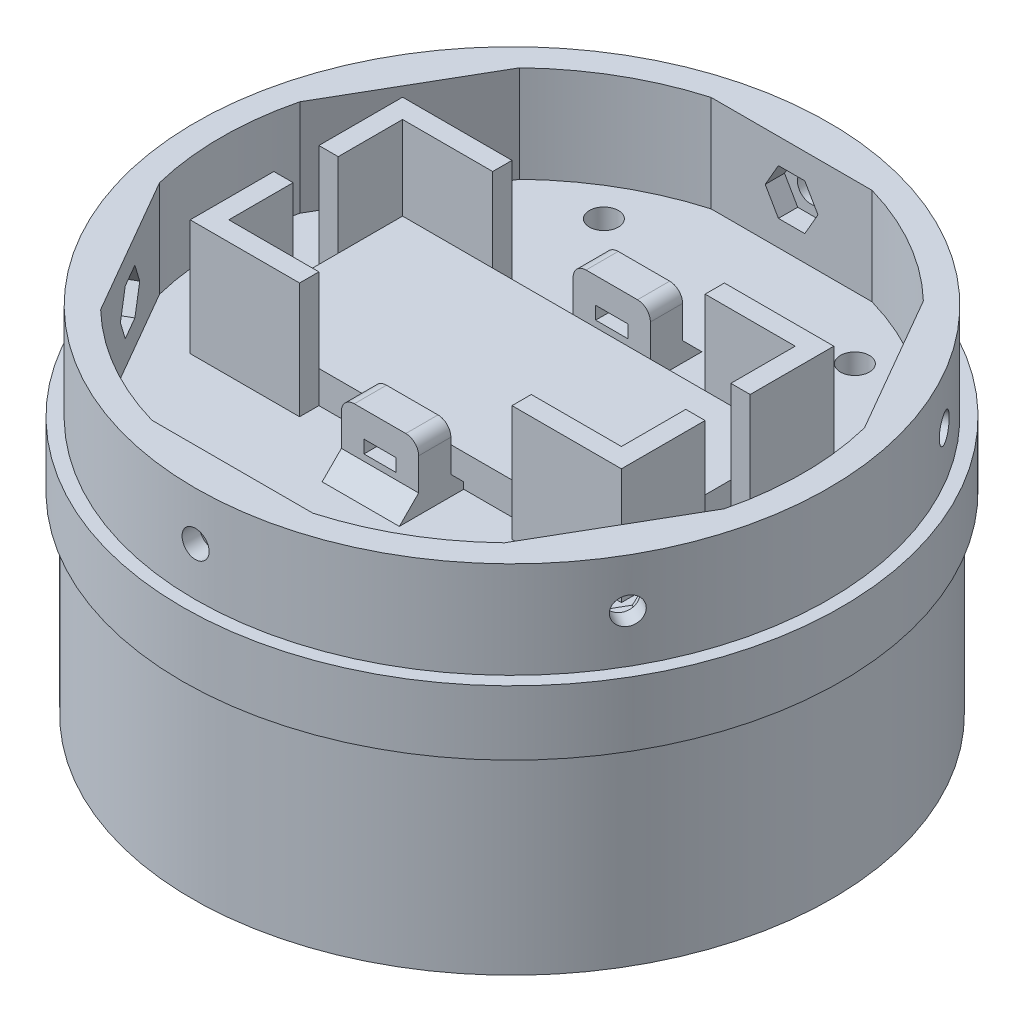
SolidWorks part; units mm, degrees
ref_plane "Спереди" through (0, 0, 0) normal (0, 0, 1) x (1, 0, 0)
ref_plane "Сверху" through (0, 0, 0) normal (0, 1, 0) x (1, 0, 0)
ref_plane "Справа" through (0, 0, 0) normal (1, 0, 0) x (0, 0, -1)
sketch "Эскиз1" plane through (0, 0, 0) normal (0, 0, 1) x (1, 0, 0)
  line L0 (0, 0) -> (0, 84.1878) construction
  line L1 (44.9, 0) -> (49.7, 0)
  line L2 (49.7, 0) -> (49.7, 30)
  line L3 (51.2, 30) -> (49.7, 30)
  line L4 (51.2, 30) -> (51.2, 40)
  line L5 (51.2, 40) -> (0, 40)
  line L6 (44.9, 5) -> (44.9, 10)
  line L7 (44.9, 35) -> (0, 35)
  line L8 (0, 35) -> (0, 40)
  line L12 (44.9, 10) -> (32.9, 10)
  line L13 (32.9, 10) -> (32.9, 15)
  line L14 (32.9, 15) -> (44.9, 15)
  line L15 (44.9, 5) -> (44.9, 0)
  line L16 (44.9, 15) -> (44.9, 35)
  dimension "D1" = 30
  dimension "D2" = 99.4
  dimension "D3" = 10
  dimension "D4" = 89.8
  dimension "D5" = 5
  dimension "D6" = 102.4
  dimension "D7" = 20
  dimension "D9" = 5
  dimension "D10" = 12
revolve "Повернуть1" add sketch "Эскиз1" angle 360 about L0
sketch "Эскиз2" plane through (0, 0, 0) normal (0, -1, 0) x (1, 0, 0)
  line L0 (0, 0) -> (50000, 0) construction
  line L1 (0, 0) -> (0, 50000) construction
  circle A0 centre (0, 0) radius 43.5 construction
  circle A4 centre (43.5, 0) radius 2.25
  dimension "D1" = 87
  dimension "D2" = 4.5
sketch "Эскиз4" plane through (0, 40, 0) normal (0, 1, 0) x (1, 0, 0)
  line L0 (0, 0) -> (50000, 0) construction
  line L1 (0, 0) -> (0, 50000) construction
  line L3 (-30.5, -13.5) -> (30.5, -13.5)
  line L4 (-30.5, -13.5) -> (-30.5, 13.5)
  line L5 (-30.5, 13.5) -> (30.5, 13.5)
  line L6 (30.5, -13.5) -> (30.5, 13.5)
  line L7 (-30.5, -13.5) -> (30.5, 13.5) construction
  line L8 (-30.5, 13.5) -> (30.5, -13.5) construction
  point P5 (0, 0)
  dimension "D1" = 27
  dimension "D2" = 61
sketch "Эскиз5" plane through (0, 40, 0) normal (0, 1, 0) x (1, 0, 0)
  line L0 (-31.3677, 32.5439) -> (0, 0) construction
  line L2 (0, 0) -> (-41.27, 23.8272) construction
  line L3 (-43.8677, 10.8933) -> (-31.3677, 32.5439)
  line L4 (-12.5, 43.4372) -> (12.5, 43.4372)
  line L5 (31.3677, 32.5439) -> (43.8677, 10.8933)
  line L6 (43.8677, -10.8933) -> (31.3677, -32.5439)
  line L7 (12.5, -43.4372) -> (-12.5, -43.4372)
  line L8 (-31.3677, -32.5439) -> (-43.8677, -10.8933)
  line L9 (0, 0) -> (0, -56.422) construction
  arc A0 (-43.8677, 10.8933) -> (-43.8677, -10.8933) centre (0, 0) ccw
  arc A3 (-12.5, 43.4372) -> (-31.3677, 32.5439) centre (0, 0) ccw
  arc A4 (31.3677, 32.5439) -> (12.5, 43.4372) centre (0, 0) ccw
  arc A5 (43.8677, -10.8933) -> (43.8677, 10.8933) centre (0, 0) ccw
  arc A6 (12.5, -43.4372) -> (31.3677, -32.5439) centre (0, 0) ccw
  arc A7 (-31.3677, -32.5439) -> (-12.5, -43.4372) centre (0, 0) ccw
  arc A8 (-43.8677, 10.8933) -> (-43.8677, -10.8933) centre (0, 0) ccw
  arc A9 (-43.8677, 10.8933) -> (-43.8677, -10.8933) centre (0, 0) ccw
  arc A10 (-43.8677, 10.8933) -> (-43.8677, -10.8933) centre (0, 0) ccw
  arc A11 (-43.8677, 10.8933) -> (-43.8677, -10.8933) centre (0, 0) ccw
  arc A12 (-43.8677, 10.8933) -> (-43.8677, -10.8933) centre (0, 0) ccw
  arc A13 (-31.3677, -32.5439) -> (-12.5, -43.4372) centre (0, 0) ccw
  arc A14 (-31.3677, -32.5439) -> (-12.5, -43.4372) centre (0, 0) ccw
  arc A15 (-31.3677, -32.5439) -> (-12.5, -43.4372) centre (0, 0) ccw
  arc A16 (-31.3677, -32.5439) -> (-12.5, -43.4372) centre (0, 0) ccw
  arc A17 (-31.3677, -32.5439) -> (-12.5, -43.4372) centre (0, 0) ccw
  arc A18 (12.5, -43.4372) -> (31.3677, -32.5439) centre (0, 0) ccw
  arc A19 (12.5, -43.4372) -> (31.3677, -32.5439) centre (0, 0) ccw
  arc A20 (12.5, -43.4372) -> (31.3677, -32.5439) centre (0, 0) ccw
  arc A21 (12.5, -43.4372) -> (31.3677, -32.5439) centre (0, 0) ccw
  arc A22 (12.5, -43.4372) -> (31.3677, -32.5439) centre (0, 0) ccw
  arc A23 (43.8677, -10.8933) -> (43.8677, 10.8933) centre (0, 0) ccw
  arc A24 (43.8677, -10.8933) -> (43.8677, 10.8933) centre (0, 0) ccw
  arc A25 (43.8677, -10.8933) -> (43.8677, 10.8933) centre (0, 0) ccw
  arc A26 (43.8677, -10.8933) -> (43.8677, 10.8933) centre (0, 0) ccw
  arc A27 (43.8677, -10.8933) -> (43.8677, 10.8933) centre (0, 0) ccw
  arc A28 (31.3677, 32.5439) -> (12.5, 43.4372) centre (0, 0) ccw
  arc A29 (31.3677, 32.5439) -> (12.5, 43.4372) centre (0, 0) ccw
  arc A30 (31.3677, 32.5439) -> (12.5, 43.4372) centre (0, 0) ccw
  arc A31 (31.3677, 32.5439) -> (12.5, 43.4372) centre (0, 0) ccw
  arc A32 (31.3677, 32.5439) -> (12.5, 43.4372) centre (0, 0) ccw
  arc A33 (-12.5, 43.4372) -> (-31.3677, 32.5439) centre (0, 0) ccw
  arc A34 (-12.5, 43.4372) -> (-31.3677, 32.5439) centre (0, 0) ccw
  arc A35 (-12.5, 43.4372) -> (-31.3677, 32.5439) centre (0, 0) ccw
  arc A36 (-12.5, 43.4372) -> (-31.3677, 32.5439) centre (0, 0) ccw
  arc A37 (-12.5, 43.4372) -> (-31.3677, 32.5439) centre (0, 0) ccw
  circle A38 centre (0, 0) radius 49.2
  circle A39 centre (0, 0) radius 51.2 construction
  point P24 (0, 0)
  dimension "D1" = 4
  dimension "D6" = 6
  dimension "D3" = 25
  dimension "D4" = 12.5
  dimension "D5" = 6
extrude "Бобышка-Вытянуть3" add sketch "Эскиз5" along normal blind 15 contours A38 A7 L8 A0 L3 A3 L4 A4 L5 A5 L6 A6 L7 region at (-47.8084, 40, 0)
sketch "Эскиз6" plane through (-37.6177, 0, -21.7186) normal (0.866, 0, 0.5) x (0.5, 0, -0.866)
  line L1 (4.0992, 47.5) -> (2.0496, 51.05)
  line L2 (2.0496, 51.05) -> (-2.0496, 51.05)
  line L3 (-2.0496, 51.05) -> (-4.0992, 47.5)
  line L4 (-12.5, 40) -> (12.5, 40)
  line L5 (12.5, 40) -> (12.5, 55)
  line L6 (12.5, 55) -> (-12.5, 55)
  line L7 (-12.5, 55) -> (-12.5, 40)
  line L8 (-12.5, 40) -> (12.5, 40)
  line L10 (12.5, 55) -> (-12.5, 55)
  line L12 (-4.0992, 47.5) -> (-2.0496, 43.95)
  line L13 (-2.0496, 43.95) -> (2.0496, 43.95)
  line L14 (2.0496, 43.95) -> (4.0992, 47.5)
  circle A0 centre (0, 47.5) radius 3.55 construction
  dimension "D2" = 7.1
  dimension "D3" = 7.5
  dimension "D1" = 0
sketch "Эскиз8" plane through (-37.6177, 0, -21.7186) normal (0.866, 0, 0.5) x (0.5, 0, -0.866)
  line L0 (0, 0) -> (0, 55) construction
  line L1 (12.5, 55) -> (-12.5, 55) construction
  circle A0 centre (0, 47.5) radius 2.1
  dimension "D1" = 4.2
sketch "Эскиз9" plane through (0, 0, 0) normal (0, -1, 0) x (1, 0, 0)
  line L0 (-200000, 0) -> (250000, 0) construction
  line L1 (0, 0) -> (39, 0) construction
  line L2 (0, 0) -> (39, 0) construction
  circle A1 centre (0, 0) radius 39 construction
  circle A2 centre (39, 0) radius 2.25
  dimension "D1" = 78
  dimension "D4" = 4.5
extrude "Вырез-Вытянуть3" cut sketch "Эскиз9" against normal blind 56
sketch "Эскиз10" plane through (0, 40, 0) normal (0, 1, 0) x (1, 0, 0)
  line L0 (30.5, -13.5) -> (30.5, 13.5) construction
  line L1 (-30.5, -13.5) -> (30.5, -13.5) construction
  line L2 (-30.5, -13.5) -> (-30.5, 13.5) construction
  line L3 (-30.5, 13.5) -> (30.5, 13.5) construction
  line L4 (30.5, -13.5) -> (30.5, -3.5)
  line L5 (-30.5, -13.5) -> (-16.5, -13.5)
  line L6 (-30.5, -13.5) -> (-30.5, -3.5)
  line L7 (-30.5, 13.5) -> (-16.5, 13.5)
  line L8 (-33.5, 3.5) -> (-30.5, 3.5)
  line L9 (-33.5, -16.5) -> (-16.5, -16.5)
  line L10 (-33.5, -16.5) -> (-33.5, -3.5)
  line L11 (-33.5, 16.5) -> (-16.5, 16.5)
  line L12 (33.5, -16.5) -> (33.5, -3.5)
  line L13 (-33.5, -16.5) -> (33.5, 16.5) construction
  line L14 (-33.5, 16.5) -> (33.5, -16.5) construction
  line L15 (-33.5, -3.5) -> (-30.5, -3.5)
  line L16 (-16.5, 16.5) -> (-16.5, 13.5)
  line L17 (16.5, 16.5) -> (16.5, 13.5)
  line L18 (-33.5, 3.5) -> (-33.5, 16.5)
  line L19 (-30.5, 3.5) -> (-30.5, 13.5)
  line L20 (30.5, -3.5) -> (33.5, -3.5)
  line L21 (-16.5, -13.5) -> (-16.5, -16.5)
  line L22 (16.5, 13.5) -> (30.5, 13.5)
  line L23 (16.5, 16.5) -> (33.5, 16.5)
  line L24 (16.5, -13.5) -> (16.5, -16.5)
  line L25 (30.5, 3.5) -> (30.5, 13.5)
  line L26 (33.5, 3.5) -> (33.5, 16.5)
  line L27 (30.5, 3.5) -> (33.5, 3.5)
  line L28 (16.5, -13.5) -> (30.5, -13.5)
  line L29 (16.5, -16.5) -> (33.5, -16.5)
  point P3 (0, 0)
  dimension "D1" = 61
  dimension "D2" = 27
  dimension "D3" = 3
  dimension "D4" = 3
  dimension "D5" = 13
  dimension "D6" = 13
  dimension "D7" = 17
  dimension "D8" = 17
extrude "Бобышка-Вытянуть4" add sketch "Эскиз10" along normal blind 18
sketch "Эскиз14" plane through (0, 0, 0) normal (0, 0, 1) x (1, 0, 0)
  line L0 (0, 0) -> (0, 55) construction
  line L1 (49.2, 55) -> (-49.2, 55) construction
  circle A0 centre (0, 47.5) radius 2.1
  dimension "D1" = 4.2
  dimension "D2" = 7.5
extrude "Бобышка-Вытянуть5" add sketch "Эскиз4" along normal blind 5
sketch "Эскиз11" plane through (0, 40, 0) normal (0, 1, 0) x (1, 0, 0)
  line L0 (0, 0) -> (50000, 0) construction
  line L1 (0, 0) -> (0, 50000) construction
  line L2 (16.5, 13.5) -> (-16.5, 13.5) construction
  line L3 (-6, 20.5) -> (6, 20.5)
  line L4 (-6, 20.5) -> (-6, 15.5)
  line L5 (-6, 15.5) -> (6, 15.5)
  line L6 (6, 20.5) -> (6, 15.5)
  line L7 (-6, 20.5) -> (6, 15.5) construction
  line L8 (-6, 15.5) -> (6, 20.5) construction
  point P5 (0, 18)
  dimension "D1" = 5
  dimension "D2" = 2
  dimension "D3" = 12
extrude "Бобышка-Вытянуть6" add sketch "Эскиз11" along normal blind 10
sketch "Эскиз12" plane through (0, 0, -20.5) normal (0, 0, -1) x (-1, 0, 0)
  line L0 (-6, 50) -> (6, 50) construction
  line L1 (-6, 50) -> (6, 50)
  line L3 (-2.5, 46) -> (2.5, 46)
  line L4 (-2.5, 46) -> (-2.5, 44)
  line L5 (-2.5, 44) -> (2.5, 44)
  line L6 (2.5, 46) -> (2.5, 44)
  line L7 (-2.5, 46) -> (2.5, 44) construction
  line L8 (-2.5, 44) -> (2.5, 46) construction
  point P0 (0, 45)
  dimension "D1" = 5
  dimension "D2" = 2
  dimension "D3" = 4
  dimension "D4" = 6
fillet "Скругление1" radius 2 2 edges at (-6, 50, -18) (6, 50, -18)
extrude "Вырез-Вытянуть4" cut sketch "Эскиз12" against normal blind 6 contours L3 L6 L5 L4
mirror "Зеркальное отражение3" about plane through (0, 0, 0) normal (0, 0, 1) of "Вырез-Вытянуть4", "Бобышка-Вытянуть6", "Скругление1"
chamfer "Фаска5" distance 3 angle 45 4 edges at (0, 40, -20.5) (0, 40, 20.5) (0, 40, -15.5) (0, 40, 15.5)
extrude "Вырез-Вытянуть6" cut sketch "Эскиз6" against normal blind 3 contours L1 L2 L3 L12 L13 L14
extrude "Вырез-Вытянуть7" cut sketch "Эскиз8" against normal blind 36 contours A0
pattern_circular "Круговой массив5" count 6 over 360 about axis through (0, 55, 0) along (0, 1, 0) of "Вырез-Вытянуть7", "Вырез-Вытянуть6"
pattern_circular "Круговой массив6" count 6 over 360 about axis through (0, 55, 0) along (0, -1, 0) of "Вырез-Вытянуть3" reverse direction yes
sketch "Эскиз13" plane through (0, 35, 0) normal (0, -1, 0) x (1, 0, 0)
  circle A0 centre (0, 0) radius 44.7095
extrude "Бобышка-Вытянуть7" add sketch "Эскиз13" against normal blind 0.4
chamfer "Фаска6" distance 3 angle 45 1 edges at (0, 35, -44.9)
